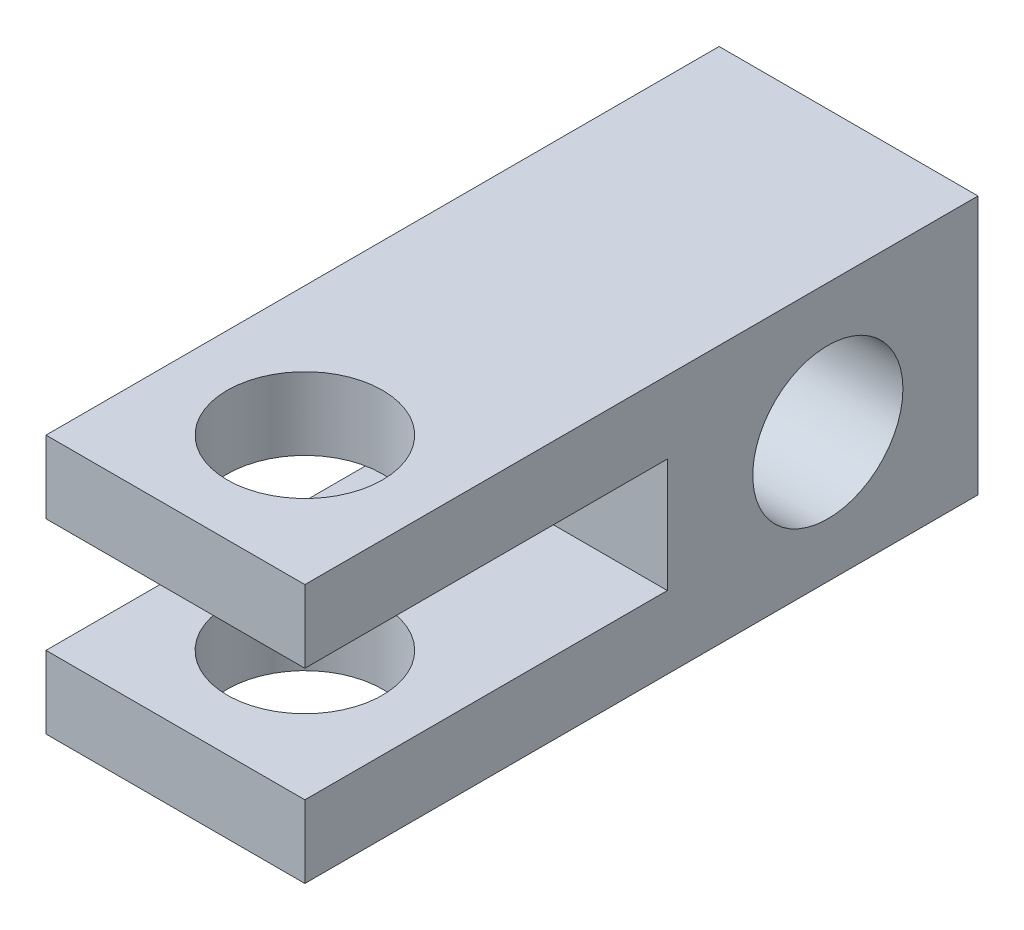
SolidWorks part; units mm, degrees
ref_plane "Front Plane" through (0, 0, 0) normal (0, 0, 1) x (1, 0, 0)
ref_plane "Top Plane" through (0, 0, 0) normal (0, 1, 0) x (1, 0, 0)
ref_plane "Right Plane" through (0, 0, 0) normal (1, 0, 0) x (0, 0, -1)
sketch "Sketch1" plane through (0, 0, 0) normal (0, 1, 0) x (1, 0, 0)
  line L1 (0, 0) -> (6.35, 0)
  line L2 (0, 0) -> (0, 16.51)
  line L3 (0, 16.51) -> (6.35, 16.51)
  line L4 (6.35, 0) -> (6.35, 16.51)
  circle A0 centre (3.175, 3.175) radius 1.905
  point P7 (0, 0)
  point P8 (3.175, 0)
  dimension "D3" = 3.81
  dimension "D1" = 6.35
  dimension "D2" = 16.51
  dimension "D4" = 3.175
extrude "Boss-Extrude1" add sketch "Sketch1" along normal blind 6.35
sketch "Sketch2" plane through (0, 0, 0) normal (0, 0, 1) x (1, 0, 0)
  line L0 (0, 6.35) -> (0, 0) construction
  line L1 (0, 1.778) -> (6.35, 1.778)
  line L2 (0, 1.778) -> (0, 4.572)
  line L3 (0, 4.572) -> (6.35, 4.572)
  line L4 (6.35, 1.778) -> (6.35, 4.572)
  line L5 (6.35, 6.35) -> (6.35, 0) construction
  point P8 (0, 3.175)
  point P9 (0, 3.175)
  dimension "D1" = 2.794
extrude "Cut-Extrude1" cut sketch "Sketch2" against normal blind 8.89 and the other way through all
sketch "Sketch4" plane through (6.35, 0, 0) normal (1, 0, 0) x (0, 0, -1)
  line L0 (8.89, 1.778) -> (8.89, 4.572) construction
  line L1 (16.51, 6.35) -> (16.51, 0) construction
  circle A0 centre (12.827, 3.175) radius 1.8415
  point P4 (8.89, 3.175)
  dimension "D1" = 3.683
  dimension "D2" = 3.683
extrude "Cut-Extrude2" cut sketch "Sketch4" against normal through all
